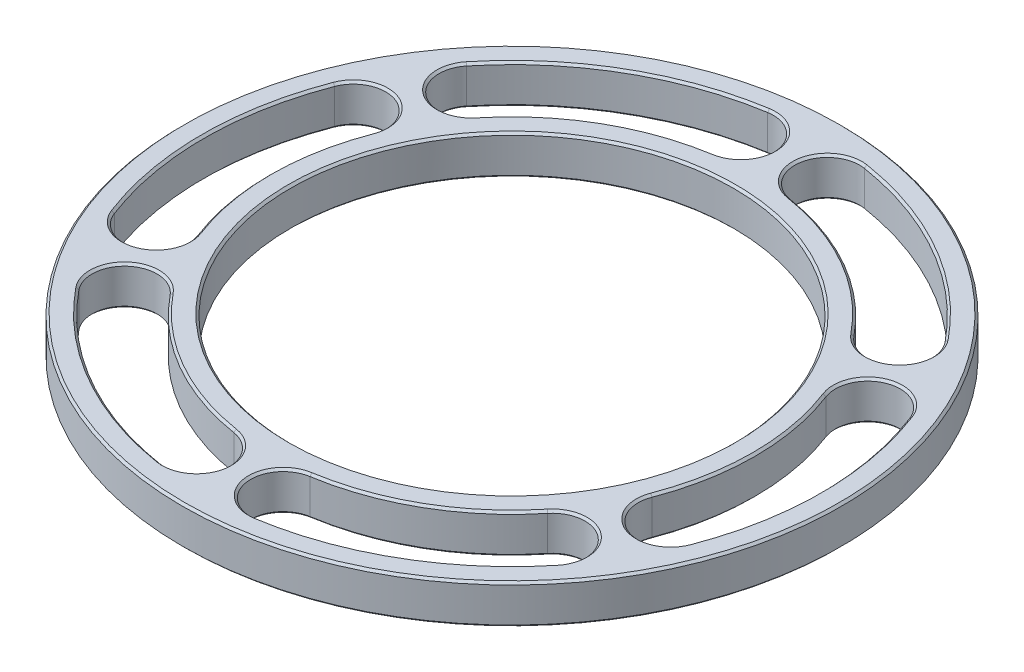
SolidWorks part; units mm, degrees
material "Delrin 2700 NC010, Low Viscosity Acetal Copolymer (SS)"
ref_plane "Front Plane" through (0, 0, 0) normal (0, 0, 1) x (1, 0, 0)
ref_plane "Top Plane" through (0, 0, 0) normal (0, 1, 0) x (1, 0, 0)
ref_plane "Right Plane" through (0, 0, 0) normal (1, 0, 0) x (0, 0, -1)
sketch "Sketch1" plane through (0, 0, 0) normal (0, 0, 1) x (1, 0, 0)
  line L0 (0, 0) -> (51.1251, 0) construction
  line L1 (51.1251, 0) -> (51.1251, 9)
  line L2 (51.1251, 9) -> (76.1, 9)
  line L3 (76.1, 9) -> (76.1, 0)
  line L4 (76.1, 0) -> (51.1251, 0)
  dimension "D1" = 9
  dimension "D2" = 51.1251
  dimension "D3" = 76.1
ref_axis "Axis1" through (0, 0, 0) along (0, 1, 0)
revolve "Revolve1" add sketch "Sketch1" angle 360 about axis through (0, 0, 0) along (0, 1, 0)
sketch "Sketch2" plane through (0, 9, 0) normal (0, 1, 0) x (1, 0, 0)
  line L0 (0, 76.1) -> (0, -76.1) construction
  line L1 (65.9045, 38.05) -> (-65.9045, -38.05) construction
  line L2 (-65.9045, 38.05) -> (65.9045, -38.05) construction
  line L3 (0, 0) -> (-63.6125, 0) construction
  line L4 (-53.1568, 33.5769) -> (-42.3753, 27.3521) construction
  line L5 (-55.6568, 29.2467) -> (-55.9334, 29.4064) construction
  circle A0 centre (0, 0) radius 76.1 construction
  arc A1 (-59.4006, 22.7624) -> (-59.4006, -22.7624) centre (0, 0) ccw construction
  arc A2 (-66.3923, 25.4416) -> (-66.3923, -25.4416) centre (0, 0) ccw
  arc A3 (-52.4089, 20.0832) -> (-52.4089, -20.0832) centre (0, 0) ccw
  arc A4 (-52.4089, 20.0832) -> (-66.3923, 25.4416) centre (-59.4006, 22.7624) ccw
  arc A5 (-66.3923, -25.4416) -> (-52.4089, -20.0832) centre (-59.4006, -22.7624) ccw
  circle A6 centre (0, 0) radius 51.1251 construction
  arc A7 (-9.9875, 62.8236) -> (-49.4131, 40.0612) centre (0, 0) ccw construction
  arc A8 (-11.163, 70.2182) -> (-55.2292, 44.7766) centre (0, 0) ccw
  arc A9 (-8.8119, 55.429) -> (-43.597, 35.3458) centre (0, 0) ccw
  arc A10 (-8.8119, 55.429) -> (-11.163, 70.2182) centre (-9.9875, 62.8236) ccw
  arc A11 (-55.2292, 44.7766) -> (-43.597, 35.3458) centre (-49.4131, 40.0612) ccw
  arc A12 (49.4131, 40.0612) -> (9.9875, 62.8236) centre (0, 0) ccw construction
  arc A13 (55.2292, 44.7766) -> (11.163, 70.2182) centre (0, 0) ccw
  arc A14 (43.597, 35.3458) -> (8.8119, 55.429) centre (0, 0) ccw
  arc A15 (43.597, 35.3458) -> (55.2292, 44.7766) centre (49.4131, 40.0612) ccw
  arc A16 (11.163, 70.2182) -> (8.8119, 55.429) centre (9.9875, 62.8236) ccw
  arc A17 (59.4006, -22.7624) -> (59.4006, 22.7624) centre (0, 0) ccw construction
  arc A18 (66.3923, -25.4416) -> (66.3923, 25.4416) centre (0, 0) ccw
  arc A19 (52.4089, -20.0832) -> (52.4089, 20.0832) centre (0, 0) ccw
  arc A20 (52.4089, -20.0832) -> (66.3923, -25.4416) centre (59.4006, -22.7624) ccw
  arc A21 (66.3923, 25.4416) -> (52.4089, 20.0832) centre (59.4006, 22.7624) ccw
  arc A22 (9.9875, -62.8236) -> (49.4131, -40.0612) centre (0, 0) ccw construction
  arc A23 (11.163, -70.2182) -> (55.2292, -44.7766) centre (0, 0) ccw
  arc A24 (8.8119, -55.429) -> (43.597, -35.3458) centre (0, 0) ccw
  arc A25 (8.8119, -55.429) -> (11.163, -70.2182) centre (9.9875, -62.8236) ccw
  arc A26 (55.2292, -44.7766) -> (43.597, -35.3458) centre (49.4131, -40.0612) ccw
  arc A27 (-49.4131, -40.0612) -> (-9.9875, -62.8236) centre (0, 0) ccw construction
  arc A28 (-55.2292, -44.7766) -> (-11.163, -70.2182) centre (0, 0) ccw
  arc A29 (-43.597, -35.3458) -> (-8.8119, -55.429) centre (0, 0) ccw
  arc A30 (-43.597, -35.3458) -> (-55.2292, -44.7766) centre (-49.4131, -40.0612) ccw
  arc A31 (-11.163, -70.2182) -> (-8.8119, -55.429) centre (-9.9875, -62.8236) ccw
  point P13 (-63.6125, 0)
  point P25 (-31.8063, 55.0901)
  point P34 (31.8063, 55.0901)
  point P41 (63.6125, 0)
  point P48 (31.8063, -55.0901)
  point P55 (-31.8063, -55.0901)
  point P60 (-54.1285, 34.2451)
  point P63 (-56.7213, 29.7541)
  dimension "D3" = 5
  dimension "D4" = 5
  dimension "D1" = 60
  dimension "D2" = 60
  dimension "D5" = 30
  dimension "D7" = 5
  dimension "D6" = 6
extrude "Cut-Extrude1" cut sketch "Sketch2" against normal blind 10 contours A2 A5 A3 A4 region at (-61.6372, 9, 0)
chamfer "Chamfer3" distance 0.5 angle 45 4 edges at (0, 0, -76.1) (0, 9, -76.1) (0, 0, -51.1251) (0, 9, -51.1251)
chamfer "Chamfer4" distance 0.5 angle 45 8 edges at (-56.7213, 9, -29.7541) (-56.7213, 0, 29.7541) (-71.1, 0, 0) (-56.1251, 0, 0) (-56.7213, 0, -29.7541) (-71.1, 9, 0) (-56.1251, 9, 0) (-56.7213, 9, 29.7541)
pattern_circular "CirPattern1" count 6 over 360 about axis through (0, 9, 0) along (0, -1, 0) of "Cut-Extrude1", "Chamfer4"
